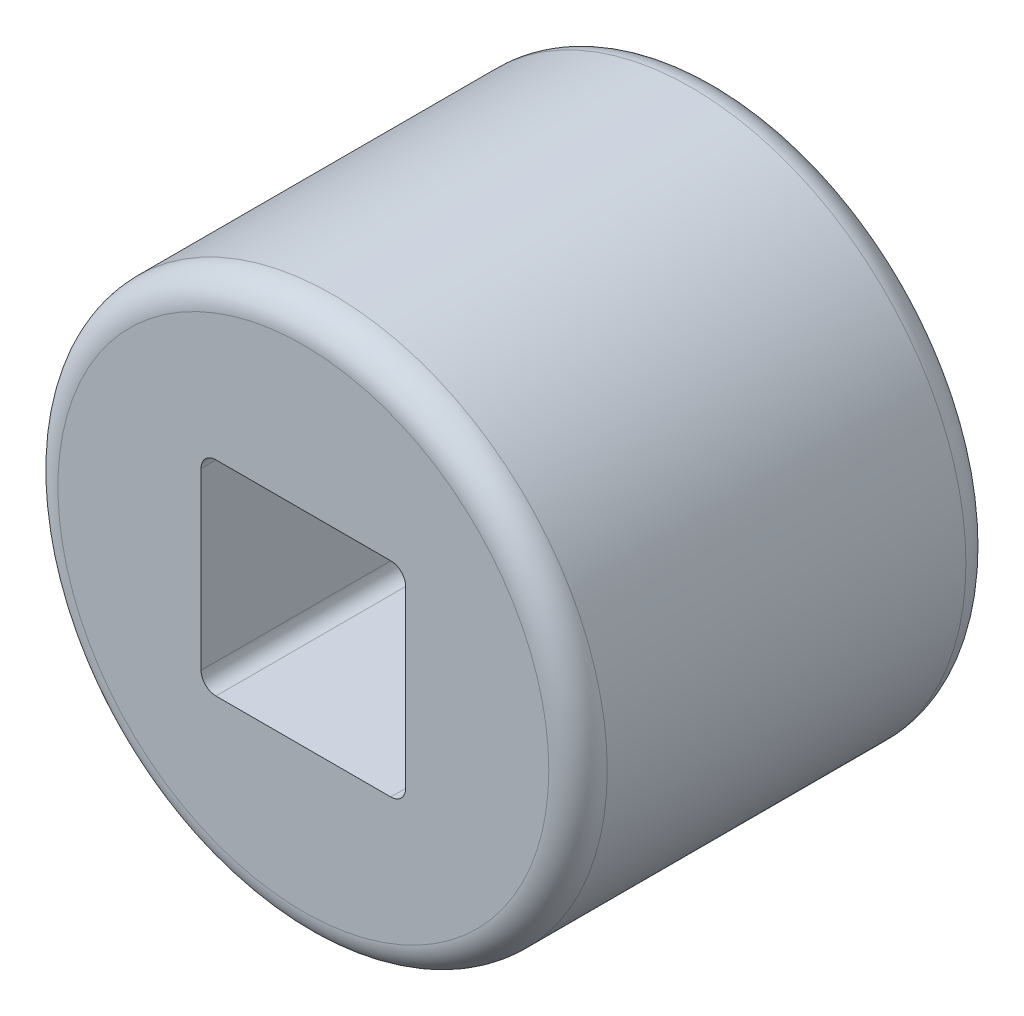
SolidWorks part; units mm, degrees
ref_plane "Front Plane" through (0, 0, 0) normal (0, 0, 1) x (1, 0, 0)
ref_plane "Top Plane" through (0, 0, 0) normal (0, 1, 0) x (1, 0, 0)
ref_plane "Right Plane" through (0, 0, 0) normal (1, 0, 0) x (0, 0, -1)
sketch "Sketch1" plane through (0, 0, 0) normal (0, 0, 1) x (1, 0, 0)
  line L1 (1.496, 1.75) -> (-1.496, 1.75)
  line L2 (1.75, 1.496) -> (1.75, -1.496)
  line L3 (1.496, -1.75) -> (-1.496, -1.75)
  line L4 (-1.75, 1.496) -> (-1.75, -1.496)
  line L5 (1.75, 1.75) -> (-1.75, -1.75) construction
  line L6 (1.75, -1.75) -> (-1.75, 1.75) construction
  circle A0 centre (0, 0) radius 4.7
  arc A1 (-1.75, -1.496) -> (-1.496, -1.75) centre (-1.496, -1.496) ccw
  arc A2 (1.496, -1.75) -> (1.75, -1.496) centre (1.496, -1.496) ccw
  arc A3 (1.75, 1.496) -> (1.496, 1.75) centre (1.496, 1.496) ccw
  arc A4 (-1.75, 1.496) -> (-1.496, 1.75) centre (-1.496, 1.496) cw
  dimension "D1" = 9.4
  dimension "D3" = 0.254
  dimension "D2" = 3.5
extrude "Boss-Extrude1" add sketch "Sketch1" along normal blind 7.1374
fillet "Fillet1" radius 0.5 2 edges at (4.7, 0, 0) (4.7, 0, 7.1374)
